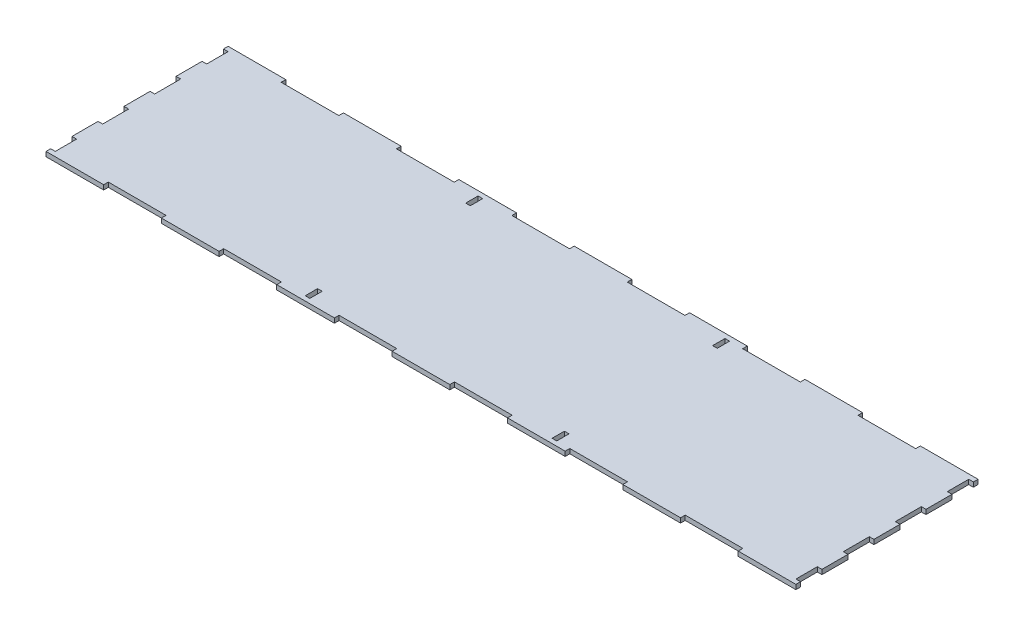
SolidWorks part; units mm, degrees
ref_plane "Front Plane" through (0, 0, 0) normal (0, 0, 1) x (1, 0, 0)
ref_plane "Top Plane" through (0, 0, 0) normal (0, 1, 0) x (1, 0, 0)
ref_plane "Right Plane" through (0, 0, 0) normal (1, 0, 0) x (0, 0, -1)
sketch "Sketch1" plane through (0, 0, 0) normal (0, 1, 0) x (1, 0, 0)
  line L0 (0, 88.9) -> (0, -88.9) construction
  line L1 (-381, 88.9) -> (381, 88.9)
  line L2 (-381, 88.9) -> (-381, -88.9)
  line L3 (-381, -88.9) -> (381, -88.9)
  line L4 (381, 88.9) -> (381, -88.9)
  line L5 (-381, 40.1411) -> (-381, 66.9018)
  line L6 (-381, 66.9018) -> (-385.7625, 66.9018)
  line L7 (-381, 66.9018) -> (-381, 93.6625)
  line L8 (-381, 93.6625) -> (-385.7625, 93.6625)
  line L9 (-385.7625, 66.9018) -> (-385.7625, 93.6625)
  line L14 (-326.4144, -88.9) -> (-385.7625, -88.9)
  line L15 (-326.4144, -88.9) -> (-326.4144, -93.6625)
  line L16 (-326.4144, -93.6625) -> (-385.7625, -93.6625)
  line L17 (-385.7625, -88.9) -> (-385.7625, -93.6625)
  line L18 (381, 66.9018) -> (385.7625, 66.9018)
  line L19 (381, 66.9018) -> (381, 93.6625)
  line L20 (381, 93.6625) -> (385.7625, 93.6625)
  line L21 (385.7625, 66.9018) -> (385.7625, 93.6625)
  line L22 (-326.4144, 88.9) -> (-385.7625, 88.9)
  line L23 (-326.4144, 88.9) -> (-326.4144, 93.6625)
  line L24 (-326.4144, 93.6625) -> (-385.7625, 93.6625)
  line L25 (-385.7625, 88.9) -> (-385.7625, 93.6625)
  line L26 (-381, 40.1411) -> (-385.7625, 40.1411)
  line L27 (-385.7625, 40.1411) -> (-385.7625, 66.9018)
  line L28 (-381, 66.9018) -> (-385.7625, 66.9018)
  line L29 (381, 40.1411) -> (381, 66.9018)
  line L30 (381, 40.1411) -> (385.7625, 40.1411)
  line L31 (385.7625, 40.1411) -> (385.7625, 66.9018)
  line L32 (381, 66.9018) -> (385.7625, 66.9018)
  line L33 (-381, 13.3804) -> (-381, 40.1411)
  line L34 (-381, 13.3804) -> (-385.7625, 13.3804)
  line L35 (-385.7625, 13.3804) -> (-385.7625, 40.1411)
  line L36 (-381, 40.1411) -> (-385.7625, 40.1411)
  line L37 (381, 13.3804) -> (381, 40.1411)
  line L38 (381, 13.3804) -> (385.7625, 13.3804)
  line L39 (385.7625, 13.3804) -> (385.7625, 40.1411)
  line L40 (381, 40.1411) -> (385.7625, 40.1411)
  line L41 (-381, -13.3804) -> (-381, 13.3804)
  line L42 (-381, -13.3804) -> (-385.7625, -13.3804)
  line L43 (-385.7625, -13.3804) -> (-385.7625, 13.3804)
  line L44 (-381, 13.3804) -> (-385.7625, 13.3804)
  line L45 (381, -13.3804) -> (381, 13.3804)
  line L46 (381, -13.3804) -> (385.7625, -13.3804)
  line L47 (385.7625, -13.3804) -> (385.7625, 13.3804)
  line L48 (381, 13.3804) -> (385.7625, 13.3804)
  line L49 (-381, -40.1411) -> (-381, -13.3804)
  line L50 (-381, -40.1411) -> (-385.7625, -40.1411)
  line L51 (-385.7625, -40.1411) -> (-385.7625, -13.3804)
  line L52 (-381, -13.3804) -> (-385.7625, -13.3804)
  line L53 (381, -40.1411) -> (381, -13.3804)
  line L54 (381, -40.1411) -> (385.7625, -40.1411)
  line L55 (385.7625, -40.1411) -> (385.7625, -13.3804)
  line L56 (381, -13.3804) -> (385.7625, -13.3804)
  line L57 (-381, -66.9018) -> (-381, -40.1411)
  line L58 (-381, -66.9018) -> (-385.7625, -66.9018)
  line L59 (-385.7625, -66.9018) -> (-385.7625, -40.1411)
  line L60 (-381, -40.1411) -> (-385.7625, -40.1411)
  line L61 (381, -66.9018) -> (381, -40.1411)
  line L62 (381, -66.9018) -> (385.7625, -66.9018)
  line L63 (385.7625, -66.9018) -> (385.7625, -40.1411)
  line L64 (381, -40.1411) -> (385.7625, -40.1411)
  line L65 (-381, -93.6625) -> (-381, -66.9018)
  line L66 (-381, -93.6625) -> (-385.7625, -93.6625)
  line L67 (-385.7625, -93.6625) -> (-385.7625, -66.9018)
  line L68 (-381, -66.9018) -> (-385.7625, -66.9018)
  line L69 (381, -93.6625) -> (381, -66.9018)
  line L70 (381, -93.6625) -> (385.7625, -93.6625)
  line L71 (385.7625, -93.6625) -> (385.7625, -66.9018)
  line L72 (381, -66.9018) -> (385.7625, -66.9018)
  line L73 (-267.0663, -88.9) -> (-267.0663, -93.6625)
  line L74 (-267.0663, -88.9) -> (-326.4144, -88.9)
  line L75 (-326.4144, -88.9) -> (-326.4144, -93.6625)
  line L76 (-267.0663, -93.6625) -> (-326.4144, -93.6625)
  line L77 (-267.0663, 88.9) -> (-267.0663, 93.6625)
  line L78 (-267.0663, 88.9) -> (-326.4144, 88.9)
  line L79 (-326.4144, 88.9) -> (-326.4144, 93.6625)
  line L80 (-267.0663, 93.6625) -> (-326.4144, 93.6625)
  line L81 (-207.7183, -88.9) -> (-207.7183, -93.6625)
  line L82 (-207.7183, -88.9) -> (-267.0663, -88.9)
  line L83 (-267.0663, -88.9) -> (-267.0663, -93.6625)
  line L84 (-207.7183, -93.6625) -> (-267.0663, -93.6625)
  line L85 (-207.7183, 88.9) -> (-207.7183, 93.6625)
  line L86 (-207.7183, 88.9) -> (-267.0663, 88.9)
  line L87 (-267.0663, 88.9) -> (-267.0663, 93.6625)
  line L88 (-207.7183, 93.6625) -> (-267.0663, 93.6625)
  line L89 (-148.3702, -88.9) -> (-148.3702, -93.6625)
  line L90 (-148.3702, -88.9) -> (-207.7183, -88.9)
  line L91 (-207.7183, -88.9) -> (-207.7183, -93.6625)
  line L92 (-148.3702, -93.6625) -> (-207.7183, -93.6625)
  line L93 (-148.3702, 88.9) -> (-148.3702, 93.6625)
  line L94 (-148.3702, 88.9) -> (-207.7183, 88.9)
  line L95 (-207.7183, 88.9) -> (-207.7183, 93.6625)
  line L96 (-148.3702, 93.6625) -> (-207.7183, 93.6625)
  line L97 (-89.0221, -88.9) -> (-89.0221, -93.6625)
  line L98 (-89.0221, -88.9) -> (-148.3702, -88.9)
  line L99 (-148.3702, -88.9) -> (-148.3702, -93.6625)
  line L100 (-89.0221, -93.6625) -> (-148.3702, -93.6625)
  line L101 (-89.0221, 88.9) -> (-89.0221, 93.6625)
  line L102 (-89.0221, 88.9) -> (-148.3702, 88.9)
  line L103 (-148.3702, 88.9) -> (-148.3702, 93.6625)
  line L104 (-89.0221, 93.6625) -> (-148.3702, 93.6625)
  line L105 (-29.674, -88.9) -> (-29.674, -93.6625)
  line L106 (-29.674, -88.9) -> (-89.0221, -88.9)
  line L107 (-89.0221, -88.9) -> (-89.0221, -93.6625)
  line L108 (-29.674, -93.6625) -> (-89.0221, -93.6625)
  line L109 (-29.674, 88.9) -> (-29.674, 93.6625)
  line L110 (-29.674, 88.9) -> (-89.0221, 88.9)
  line L111 (-89.0221, 88.9) -> (-89.0221, 93.6625)
  line L112 (-29.674, 93.6625) -> (-89.0221, 93.6625)
  line L113 (29.674, -88.9) -> (29.674, -93.6625)
  line L114 (29.674, -88.9) -> (-29.674, -88.9)
  line L115 (-29.674, -88.9) -> (-29.674, -93.6625)
  line L116 (29.674, -93.6625) -> (-29.674, -93.6625)
  line L117 (29.674, 88.9) -> (29.674, 93.6625)
  line L118 (29.674, 88.9) -> (-29.674, 88.9)
  line L119 (-29.674, 88.9) -> (-29.674, 93.6625)
  line L120 (29.674, 93.6625) -> (-29.674, 93.6625)
  line L121 (89.0221, -88.9) -> (89.0221, -93.6625)
  line L122 (89.0221, -88.9) -> (29.674, -88.9)
  line L123 (29.674, -88.9) -> (29.674, -93.6625)
  line L124 (89.0221, -93.6625) -> (29.674, -93.6625)
  line L125 (89.0221, 88.9) -> (89.0221, 93.6625)
  line L126 (89.0221, 88.9) -> (29.674, 88.9)
  line L127 (29.674, 88.9) -> (29.674, 93.6625)
  line L128 (89.0221, 93.6625) -> (29.674, 93.6625)
  line L129 (148.3702, -88.9) -> (148.3702, -93.6625)
  line L130 (148.3702, -88.9) -> (89.0221, -88.9)
  line L131 (89.0221, -88.9) -> (89.0221, -93.6625)
  line L132 (148.3702, -93.6625) -> (89.0221, -93.6625)
  line L133 (148.3702, 88.9) -> (148.3702, 93.6625)
  line L134 (148.3702, 88.9) -> (89.0221, 88.9)
  line L135 (89.0221, 88.9) -> (89.0221, 93.6625)
  line L136 (148.3702, 93.6625) -> (89.0221, 93.6625)
  line L137 (207.7183, -88.9) -> (207.7183, -93.6625)
  line L138 (207.7183, -88.9) -> (148.3702, -88.9)
  line L139 (148.3702, -88.9) -> (148.3702, -93.6625)
  line L140 (207.7183, -93.6625) -> (148.3702, -93.6625)
  line L141 (207.7183, 88.9) -> (207.7183, 93.6625)
  line L142 (207.7183, 88.9) -> (148.3702, 88.9)
  line L143 (148.3702, 88.9) -> (148.3702, 93.6625)
  line L144 (207.7183, 93.6625) -> (148.3702, 93.6625)
  line L145 (267.0663, -88.9) -> (267.0663, -93.6625)
  line L146 (267.0663, -88.9) -> (207.7183, -88.9)
  line L147 (207.7183, -88.9) -> (207.7183, -93.6625)
  line L148 (267.0663, -93.6625) -> (207.7183, -93.6625)
  line L149 (267.0663, 88.9) -> (267.0663, 93.6625)
  line L150 (267.0663, 88.9) -> (207.7183, 88.9)
  line L151 (207.7183, 88.9) -> (207.7183, 93.6625)
  line L152 (267.0663, 93.6625) -> (207.7183, 93.6625)
  line L185 (326.4144, -88.9) -> (326.4144, -93.6625)
  line L186 (326.4144, -88.9) -> (267.0663, -88.9)
  line L187 (267.0663, -88.9) -> (267.0663, -93.6625)
  line L188 (326.4144, -93.6625) -> (267.0663, -93.6625)
  line L189 (326.4144, 88.9) -> (326.4144, 93.6625)
  line L190 (326.4144, 88.9) -> (267.0663, 88.9)
  line L191 (267.0663, 88.9) -> (267.0663, 93.6625)
  line L192 (326.4144, 93.6625) -> (267.0663, 93.6625)
  line L193 (385.7625, -88.9) -> (385.7625, -93.6625)
  line L194 (385.7625, -88.9) -> (326.4144, -88.9)
  line L195 (326.4144, -88.9) -> (326.4144, -93.6625)
  line L196 (385.7625, -93.6625) -> (326.4144, -93.6625)
  line L197 (385.7625, 88.9) -> (385.7625, 93.6625)
  line L198 (385.7625, 88.9) -> (326.4144, 88.9)
  line L199 (326.4144, 88.9) -> (326.4144, 93.6625)
  line L200 (385.7625, 93.6625) -> (326.4144, 93.6625)
  point P8 (0, 88.9)
  point P9 (0, 0)
  dimension "D1" = 762
  dimension "D2" = 177.8
  dimension "D3" = 187.325
  dimension "D5" = 771.525
  dimension "D6" = 26.7607
  dimension "D8" = 59.3481
  dimension "D4" = 7
  dimension "D7" = 13
extrude "Boss-Extrude1" add sketch "Sketch1" along normal blind 4.7625 contours L0 L1 L2 L3 | L126 L0 L122 L3 L4 L1 | L65 L16 L15 L3 | L16 L65 L14 L17 | L84 L81 L3 L73 | L59 L58 L2 L50 | L100 L97 L3 L89 | L43 L42 L2 L34 | L27 L26 L2 L6 | L22 L7 L8 L9 | L23 L24 L7 L1 | L85 L88 L77 L1 | L101 L104 L93 L1 | L117 L120 L109 L1 | L133 L136 L125 L1 | L116 L113 L3 L105 | L132 L129 L3 L121 | L148 L145 L3 L137 | L149 L152 L141 L1 | L21 L20 L19 | L30 L31 L18 L4 | L46 L47 L38 L4 | L62 L63 L54 L4 | L71 L69 L70 | L193 L196 L195 L194 | L197 L200 L199 L198 region at (190.5, 0, 0) region at (-190.5, 0, 0) region at (0, 0, -91.2812) region at (0, 0, 91.2812) region at (-118.6962, 0, -91.2812) region at (118.6962, 0, -91.2812) region at (-118.6962, 0, 91.2812) region at (118.6962, 0, 91.2812) region at (-237.3923, 0, -91.2812) region at (237.3923, 0, -91.2812) region at (-237.3923, 0, 91.2812) region at (237.3923, 0, 91.2812) region at (-353.7072, 0, -91.2812) region at (-353.7072, 0, 91.2812) region at (-383.3812, 0, -91.2812) region at (383.3813, 0, -91.2812) region at (-383.3812, 0, 91.2813) region at (383.3813, 0, 91.2812) region at (-383.3812, 0, -53.5214) region at (383.3813, 0, -53.5214) region at (-383.3812, 0, 53.5214) region at (383.3813, 0, 53.5214) region at (-383.3812, 0, 0) region at (383.3813, 0, 0)
sketch "Sketch2" plane through (0, 4.7625, 0) normal (0, 1, 0) x (1, 0, 0)
  line L0 (-124.6188, 0) -> (124.6188, 0) construction
  line L1 (-129.3812, 15.4404) -> (-124.6188, 15.4404) construction
  line L2 (-129.3812, 15.4404) -> (-129.3812, -15.4404) construction
  line L3 (-129.3812, -15.4404) -> (-124.6188, -15.4404) construction
  line L4 (-124.6188, 15.4404) -> (-124.6188, -15.4404) construction
  line L5 (124.6188, 14.3164) -> (129.3812, 14.3164) construction
  line L6 (124.6188, 14.3164) -> (124.6188, -14.3164) construction
  line L7 (124.6188, -14.3164) -> (129.3812, -14.3164) construction
  line L8 (129.3812, 14.3164) -> (129.3812, -14.3164) construction
  line L9 (-130.175, 24.6215) -> (-123.825, 24.6215) construction
  line L10 (-127, 24.6215) -> (-127, 15.4404) construction
  line L12 (-123.825, 76.2) -> (-119.0625, 76.2)
  line L13 (-123.825, 76.2) -> (-123.825, 88.9)
  line L14 (-123.825, 88.9) -> (-119.0625, 88.9)
  line L15 (-119.0625, 76.2) -> (-119.0625, 88.9)
  line L16 (-123.825, 24.6215) -> (-123.825, 76.2) construction
  line L18 (-119.0625, -88.9) -> (-123.825, -88.9)
  line L19 (-119.0625, -88.9) -> (-119.0625, -76.2)
  line L20 (-119.0625, -76.2) -> (-123.825, -76.2)
  line L21 (-123.825, -88.9) -> (-123.825, -76.2)
  line L31 (-207.7183, 88.9) -> (-148.3702, 88.9) construction
  line L32 (-207.7183, -88.9) -> (-148.3702, -88.9) construction
  line L33 (130.175, 76.2) -> (130.175, 88.9)
  line L34 (130.175, 76.2) -> (134.9375, 76.2)
  line L35 (134.9375, 76.2) -> (134.9375, 88.9)
  line L36 (130.175, 88.9) -> (134.9375, 88.9)
  line L37 (134.9375, -88.9) -> (134.9375, -76.2)
  line L38 (134.9375, -88.9) -> (130.175, -88.9)
  line L39 (130.175, -88.9) -> (130.175, -76.2)
  line L40 (134.9375, -76.2) -> (130.175, -76.2)
  line L41 (123.825, 24.6215) -> (130.175, 24.6215) construction
  line L42 (127, 24.6215) -> (127, 14.3164) construction
  line L43 (130.175, 24.6215) -> (130.175, 76.2) construction
  point P10 (0, 0)
  point P43 (127, 14.3164)
  dimension "D1" = 4.7625
  dimension "D2" = 6.35
  dimension "D4" = 4.7625
  dimension "D5" = 12.7
  dimension "D3" = 254
  dimension "D6" = 2
extrude "Cut-Extrude1" cut sketch "Sketch2" against normal through all
equation "\"Height\"= 12in"
equation "\"Depth\"= 7in"
equation "\"WallThickness\"= 0.1875in"
equation "\"FloorThickness\"= 0.1875in"
equation "\"D1@Sketch1\"=\"Width\""
equation "\"D2@Sketch1\"=\"Depth\""
equation "\"D3@Sketch1\"=\"D2@Sketch1\"+2*\"WallThickness\""
equation "\"D5@Sketch1\"=\"D1@Sketch1\"+2*\"WallThickness\""
equation "\"D6@Sketch1\"=\"D3@Sketch1\"/\"D4@Sketch1\""
equation "\"D8@Sketch1\"=\"D5@Sketch1\"/\"D7@Sketch1\""
equation "\"D1@Boss-Extrude1\"=\"FloorThickness\""
equation "\"D1@Sketch2\"=\"WallThickness\""
equation "\"D2@Sketch2\"=\"WallThickness\"+(1/16in)"
equation "\"D4@Sketch2\"=\"WallThickness\""
equation "\"Width\"= 30in"
